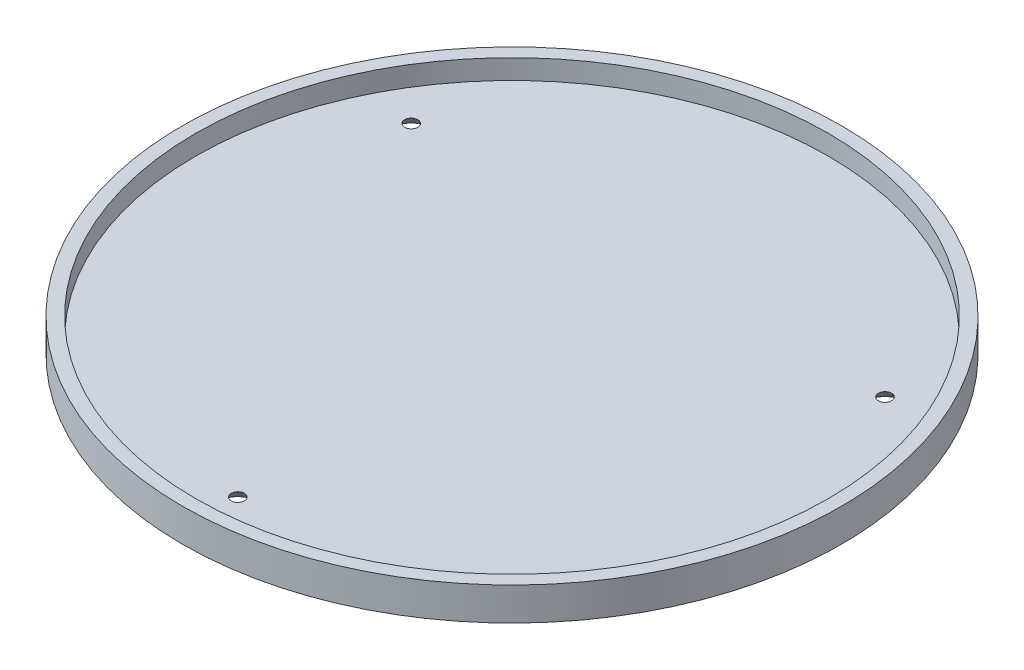
SolidWorks part; units mm, degrees
ref_plane "前视基准面" through (0, 0, 0) normal (0, 0, 1) x (1, 0, 0)
ref_plane "上视基准面" through (0, 0, 0) normal (0, 1, 0) x (1, 0, 0)
ref_plane "右视基准面" through (0, 0, 0) normal (1, 0, 0) x (0, 0, -1)
sketch "草图1" plane through (0, 0, 0) normal (0, 1, 0) x (1, 0, 0)
  circle A0 centre (0, 0) radius 50
extrude "凸台-拉伸1" add sketch "草图1" along normal blind 2
sketch "草图2" plane through (0, 2, 0) normal (0, 1, 0) x (1, 0, 0)
  circle A0 centre (0, 0) radius 50
  circle A1 centre (0, 0) radius 48
extrude "凸台-拉伸2" add sketch "草图2" along normal blind 3
sketch "草图3" plane through (0, 0, 0) normal (0, -1, 0) x (1, 0, 0)
  circle A0 centre (0, 41.5985) radius 1
  circle A1 centre (-35.9401, -20.6515) radius 1
  circle A2 centre (35.9401, -20.6515) radius 1
extrude "切除-拉伸1" cut sketch "草图3" against normal blind 20
fillet "圆角1" radius 2 3 edges at (0, 0, 40.5985) (35.9401, 0, -21.6515) (-35.9401, 0, -21.6515) conic radius 10
